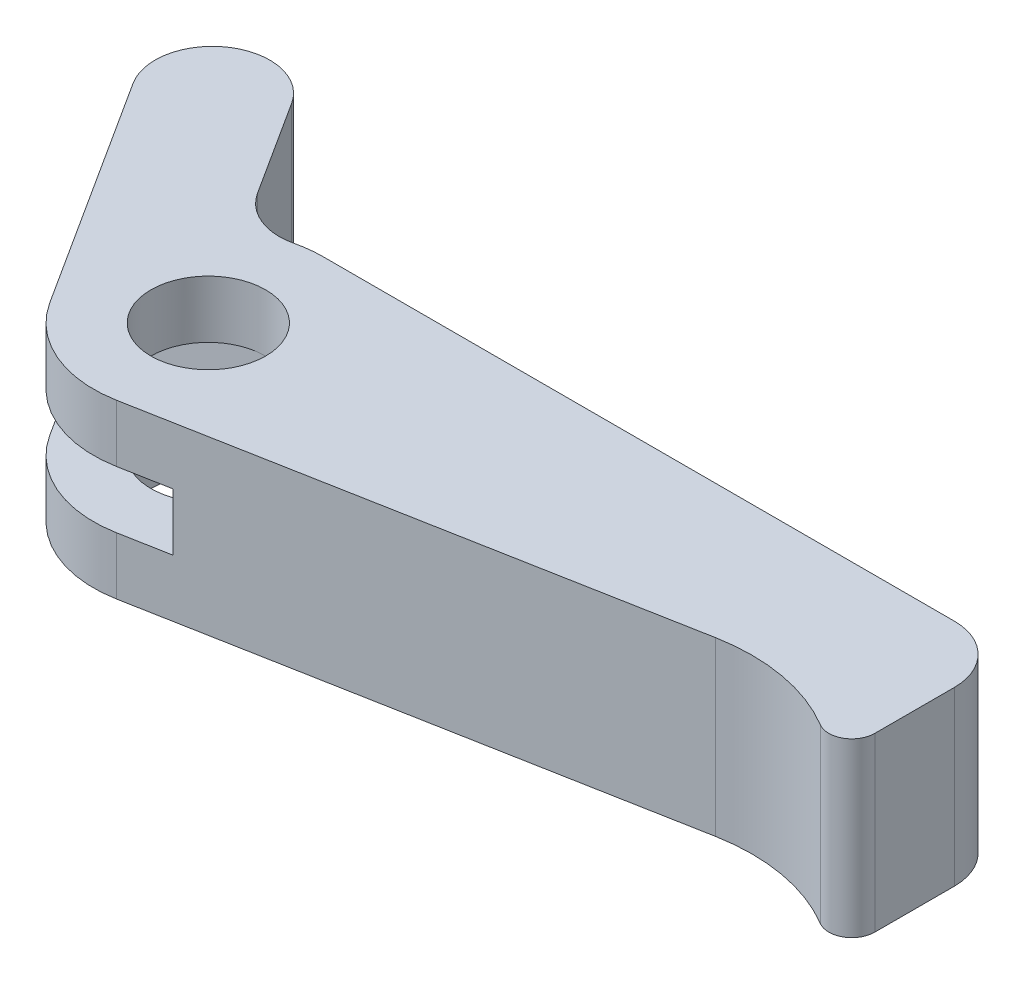
SolidWorks part; units mm, degrees
material "6061-T6 (SS)"
ref_plane "Front" through (0, 0, 0) normal (0, 0, 1) x (1, 0, 0)
ref_plane "Top" through (0, 0, 0) normal (0, 1, 0) x (1, 0, 0)
ref_plane "Right" through (0, 0, 0) normal (1, 0, 0) x (0, 0, -1)
sketch "Sketch1" plane through (0, 0, 0) normal (0, 1, 0) x (1, 0, 0)
  line L0 (0, 6.35) -> (38.1, 6.35)
  line L1 (38.1, 6.35) -> (38.1, -3.81)
  line L2 (1.1609, -6.243) -> (29.1009, -1.0476)
  line L3 (-3.4246, 5.3474) -> (-9.9315, 15.5074)
  line L4 (-9.9315, 15.5074) -> (-15.2788, 12.0827)
  line L5 (-15.2788, 12.0827) -> (-5.3474, -3.4246)
  circle A0 centre (0, 0) radius 3.175
  circle A1 centre (0, 0) radius 6.35
  arc A2 (29.1009, -1.0476) -> (38.1, -3.81) centre (30.9582, -11.0364) cw
  point P12 (-6.2622, -1.0476)
  point P13 (-6.2627, -1.0476)
  point P16 (-17.3197, 10.1614)
  point P17 (-16.1957, 11.8711)
  dimension "D1" = 6.35
  dimension "D2" = 12.7
  dimension "D5" = 27.94
  dimension "D7" = 12.065
  dimension "D6" = 10.16
  dimension "D3" = 38.1
  dimension "D4" = 10.16
  dimension "D8" = 6.35
  dimension "D9" = 10.16
extrude "Boss-Extrude1" add sketch "Sketch1" along normal blind 9.525 contours A1 A0 | L2 A2 L1 L0 A1 | A1 L3 L4 L5 region at (20.3475, 0, -1.6974) region at (4.3631, 0, -4.3631) region at (-9.094, 0, -7.9821)
fillet "Fillet1" radius 3.175 4 edges at (38.1, 4.7625, -6.35) (-3.4246, 4.7625, -5.3474) (-15.2788, 4.7625, -12.0827) (-9.9315, 4.7625, -15.5074)
fillet "Fillet2" radius 1.27 1 edges at (38.1, 4.7625, 3.81)
ref_plane "Plane2" through (0, 0, 6.35) normal (0, 0, 1) x (1, 0, 0)
sketch "Sketch8" plane through (0, 0, 6.35) normal (0, 0, 1) x (1, 0, 0)
  line L0 (-8.89, 6.35) -> (-8.89, 3.175)
  line L1 (1.1609, 9.525) -> (1.1609, 0) construction
  line L2 (-8.89, 6.35) -> (3.81, 6.35)
  line L3 (3.81, 6.35) -> (3.81, 3.175)
  line L4 (3.81, 3.175) -> (-8.89, 3.175)
  point P2 (0, 0)
  point P5 (1.1609, 4.7625)
  point P6 (-8.89, 4.7625)
  point P9 (0, 0)
  point P11 (4.6676, 3.175)
  dimension "D1" = 3.175
  dimension "D2" = 12.7
  dimension "D3" = 0.635
extrude "Cut-Extrude1" cut sketch "Sketch8" against normal blind 9.525
